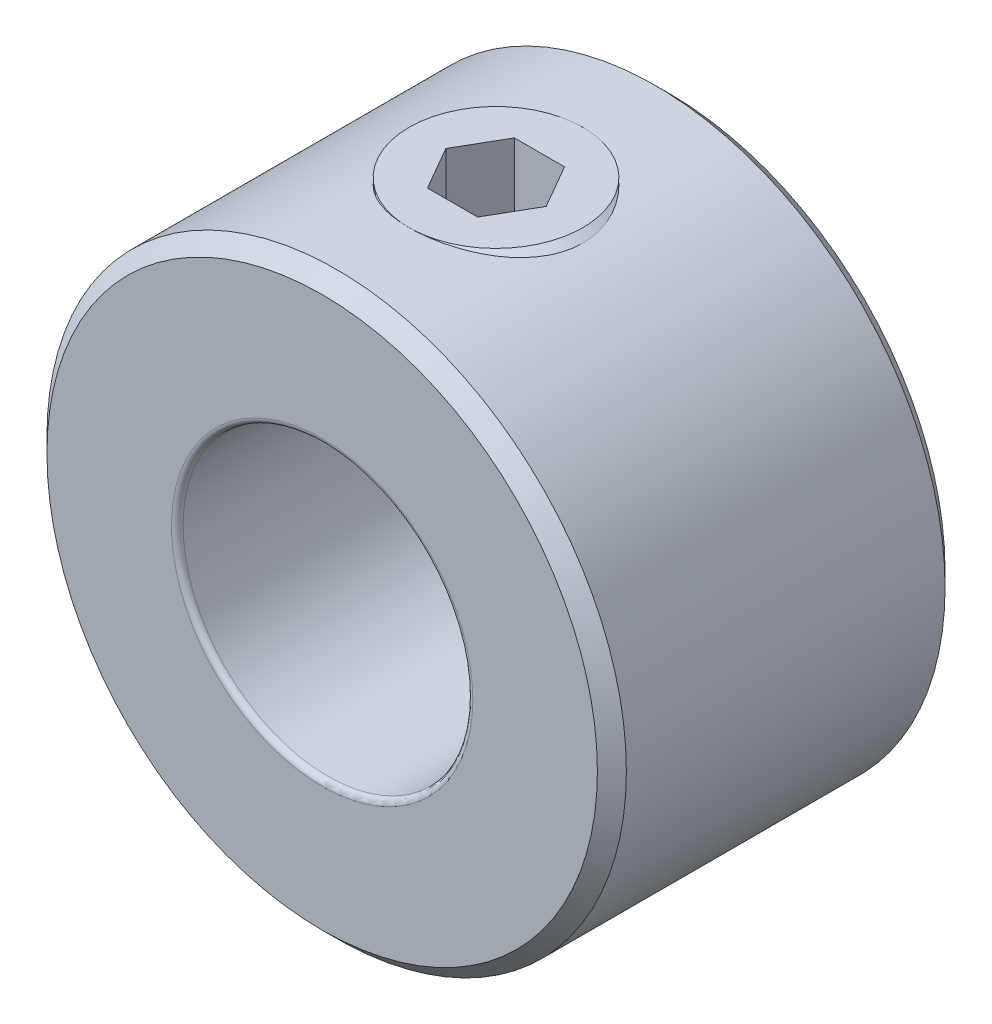
SolidWorks part; units mm, degrees
ref_plane "Front Plane" through (0, 0, 0) normal (0, 0, 1) x (1, 0, 0)
ref_plane "Top Plane" through (0, 0, 0) normal (0, 1, 0) x (1, 0, 0)
ref_plane "Right Plane" through (0, 0, 0) normal (1, 0, 0) x (0, 0, -1)
sketch "Sketch1" plane through (0, 0, 0) normal (0, 0, 1) x (1, 0, 0)
  line L0 (0, 5) -> (0, 0) construction
  line L1 (0, 0) -> (-3.5355, -3.5355) construction
  circle A0 centre (0, 0) radius 5
  circle A1 centre (0, 0) radius 2.5
  point P4 (5, 0)
  point P5 (0, 5)
  dimension "Bore Dia" = 5
  dimension "OD" = 10
  dimension "D1" = 135
extrude "Extrude1" add sketch "Sketch1" along normal blind 6
ref_plane "Plane1" through (0, 5, 0) normal (0, 1, 0) x (-1, 0, 0)
sketch "Sketch2" plane through (0, 5, 0) normal (0, 1, 0) x (-1, 0, 0)
  line L0 (0, 0) -> (0, 6) construction
  line L2 (5, 6) -> (-5, 6) construction
  circle A0 centre (0, 3) radius 1.5
  point P8 (0, 3)
  dimension "Set Screw Dia" = 3
extrude "Cut-Extrude1" cut sketch "Sketch2" against normal up to surface (5 mm away) up to plane "Top Plane"
ref_plane "Plane2" through (0, 0, 3) normal (0, 0, 1) x (1, 0, 0)
sketch "Sketch3" plane through (0, 0, 3) normal (0, 0, 1) x (1, 0, 0)
  line L0 (-1.35, 5) -> (-1.5, 4.895)
  line L1 (0, 1.4939) -> (0, 5)
  line L3 (-1.5, 1.6781) -> (-1.5, 4.895)
  line L4 (0, 5) -> (-1.35, 5)
  line L5 (0, 1) -> (0, 0) construction
  line L6 (-1.5, 4.895) -> (0, 4.895) construction
  line L7 (0, 1.4939) -> (-0.8219, 1)
  line L8 (-0.8219, 1) -> (-1.5, 1.6781)
  point P1 (-0.8219, 1)
  dimension "Screw Length" = 4
  dimension "D3" = 3
  dimension "D1" = 2.7
  dimension "D7" = 1.5
  dimension "D2" = 35
  dimension "D4" = 59
  dimension "D5" = 45
revolve "Revolve1" add sketch "Sketch3" angle 360 about L1
sketch "Sketch4" plane through (0, 5, 0) normal (0, 1, 0) x (0, 0, -1)
  line L0 (-3, 0.866) -> (-3, -0.866) construction
  line L1 (-3, 0.866) -> (-3.75, 0.433)
  line L2 (-3.75, 0.433) -> (-3.75, -0.433)
  line L3 (-3.75, -0.433) -> (-3, -0.866)
  line L4 (-3, -0.866) -> (-2.25, -0.433)
  line L5 (-2.25, -0.433) -> (-2.25, 0.433)
  line L6 (-2.25, 0.433) -> (-3, 0.866)
  circle A0 centre (-3, 0) radius 0.75 construction
  circle A1 centre (-3, 0) radius 0.866 construction
  dimension "D1" = 1.7321
  dimension "Hex" = 1.5
extrude "Cut-Extrude2" cut sketch "Sketch4" against normal blind 1.2
fillet "Fillet1" radius 0.1 2 edges at (2.5, 0, 0) (2.5, 0, 6)
chamfer "Chamfer1" distance 0.25 angle 45 2 edges at (5, 0, 6) (5, 0, 0)
sketch "Sketch5" plane through (0, 5, 0) normal (0, 1, 0) x (1, 0, 0)
  circle A0 centre (0, -3) radius 1.5 construction
  circle A1 centre (0, -3) radius 1.5
curve "Helix/Spiral1" pitch 0.5 height 4 radius 1.5 centre (0, 5, 3) axis (0, -1, 0) start towards (-1, 0, 0) parameters "Pitch"=0.5
ref_plane "Plane3" through (0, 0, 3) normal (0, 0, 1) x (1, 0, 0)
sketch "Sketch9" plane through (0, 0, 3) normal (0, 0, 1) x (1, 0, 0)
  line L0 (-1.5, 5) -> (-1.5, 5.4375)
  line L1 (-1.5, 5.4375) -> (-1.1752, 5.25)
  line L2 (-1.1752, 5.25) -> (-1.1752, 5.1875)
  line L3 (-1.1752, 5.1875) -> (-1.5, 5)
  line L4 (-1.5, 5.2188) -> (-1.1752, 5.2188) construction
  line L5 (-1.3376, 5.0938) -> (-1.3376, 5.3438) construction
  dimension "D1" = 0.0625
  dimension "D2" = 0.25
  dimension "D3" = 60
sweep "Cut-Sweep2" cut profiles "Sketch9" path "Helix/Spiral1" align with end faces yes
sketch "Sketch10" plane through (0, 5, 0) normal (0, 1, 0) x (1, 0, 0)
  line L0 (-0.433, -2.25) -> (-0.866, -3) construction
  line L1 (-0.866, -3) -> (-0.433, -3.75) construction
  line L2 (-0.433, -3.75) -> (0.433, -3.75) construction
  line L3 (0.433, -3.75) -> (0.866, -3) construction
  line L4 (0.866, -3) -> (0.433, -2.25) construction
  line L5 (0.433, -2.25) -> (-0.433, -2.25) construction
  line L6 (-0.433, -2.25) -> (-0.866, -3)
  line L7 (-0.866, -3) -> (-0.433, -3.75)
  line L8 (-0.433, -3.75) -> (0.433, -3.75)
  line L9 (0.433, -3.75) -> (0.866, -3)
  line L10 (0.866, -3) -> (0.433, -2.25)
  line L11 (0.433, -2.25) -> (-0.433, -2.25)
  circle A0 centre (0, -3) radius 1.5 construction
  circle A1 centre (0, -3) radius 1.5
extrude "Boss-Extrude1" add sketch "Sketch10" against normal through all draft 60
ref_plane "Contact Plane 1" through (0, 0, 6) normal (0, 0, 1) x (1, 0, 0)
ref_plane "Contact Plane 2" through (0, 0, 0) normal (0, 0, -1) x (-1, 0, 0)
ref_plane "Contact Plane 3" through (0, 1, 0) normal (0, -1, 0) x (-1, 0, 0)
ref_axis "Central Axis 1" through (0, 0, 5.9) along (0, 0, -1)
equation "\"D1@Fillet1\" = \"OD@Sketch1\"*.01"
equation "\"D1@Cut-Extrude2\" = \"Hex@Sketch4\"*.8"
equation "\"D3@Sketch3\"=\"Set Screw Dia@Sketch2\""
equation "\"D1@Sketch3\"=\"Set Screw Dia@Sketch2\"*.9"
equation "\"D3@Helix/Spiral1\"=\"Screw Length@Sketch3\""
equation "\"D1@Sketch9\"=\"Pitch@Helix/Spiral1\"*.125"
equation "\"D2@Sketch9\"=\"Pitch@Helix/Spiral1\"*.50"
